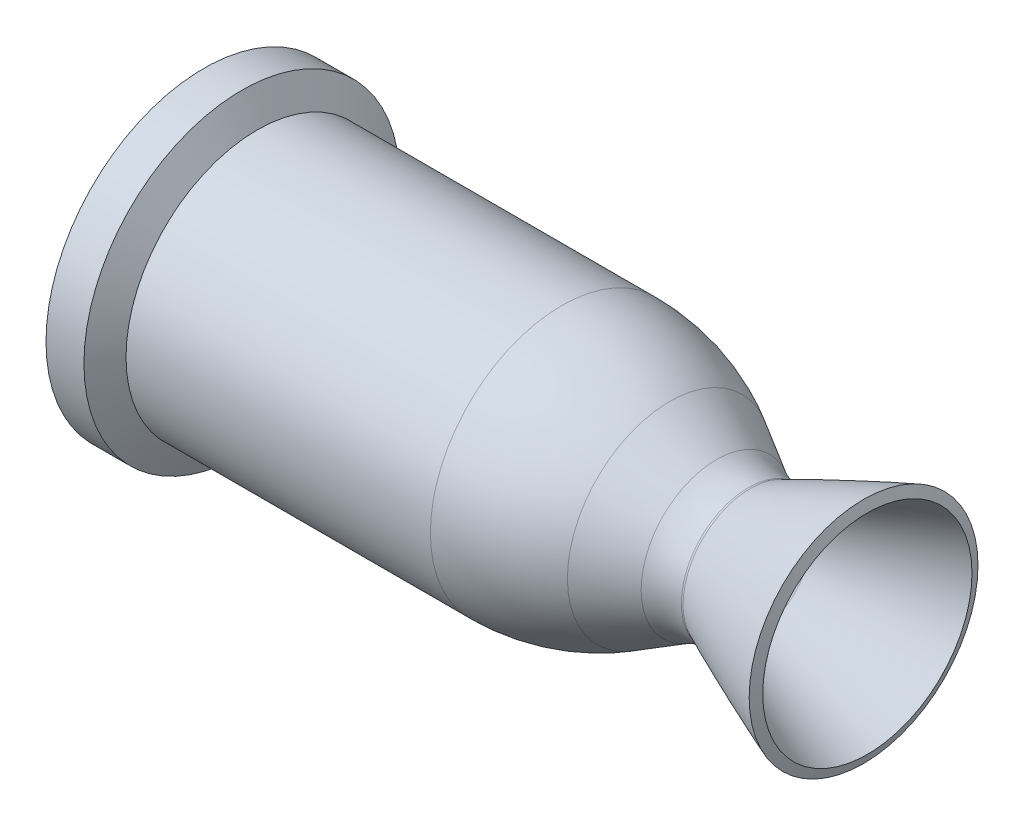
SolidWorks part; units mm, degrees
ref_plane "Front Plane" through (0, 0, 0) normal (0, 0, 1) x (1, 0, 0)
ref_plane "Top Plane" through (0, 0, 0) normal (0, 1, 0) x (1, 0, 0)
ref_plane "Right Plane" through (0, 0, 0) normal (1, 0, 0) x (0, 0, -1)
sketch "Sketch2" plane through (0, 0, 0) normal (0, 0, 1) x (1, 0, 0)
  line L0 (0, 55.5012) -> (144.9347, 55.5012)
  line L1 (192.877, 42.655) -> (215.1271, 29.8089)
  line L2 (0, 0) -> (370.4363, 0) construction
  line L3 (0, 0) -> (0, 55.5012) construction
  line L4 (0, 0) -> (290.4856, 0) construction
  line L5 (290.4856, 0) -> (290.4856, 47.6713) construction
  arc A0 (192.877, 42.655) -> (144.9347, 55.5012) centre (144.9346, -40.3836) ccw
  arc A1 (215.1271, 29.8089) -> (233.7428, 24.8208) centre (233.7428, 62.0521) ccw
  arc A2 (233.7428, 24.8208) -> (237.5976, 25.6398) centre (233.7428, 34.3024) ccw
  spline S0 degree 2 poles (237.5976, 25.6398) (305.7949, 55.9872) (370.4363, 74.9571) knots 0 0 0 1 1 1
  dimension "D4" = 95.8847
  dimension "D5" = 37.2313
  dimension "D6" = 9.4816
  dimension "D1" = 111.0023
  dimension "D2" = 49.6417
  dimension "D3" = 149.9142
  dimension "D7" = 144.9347
  dimension "D8" = 233.7428
  dimension "D9" = 370.4363
  dimension "D10" = 192.877
  dimension "D11" = 215.1271
  dimension "D12" = 237.5976
  dimension "D13" = 30
  dimension "D14" = 290.4856
sketch "Sketch3" plane through (0, 0, 0) normal (0, 0, 1) x (1, 0, 0)
  line L3 (0, 62.5012) -> (144.9347, 62.5012)
  line L4 (196.377, 48.7172) -> (218.6271, 35.871)
  line L5 (193.877, 44.3871) -> (216.1272, 31.5409)
  line L6 (0, 57.5012) -> (144.9347, 57.5012)
  line L7 (193.877, 44.3871) -> (216.1272, 31.5409)
  line L8 (0, 57.5012) -> (144.9347, 57.5012)
  line L9 (0, 57.5012) -> (0, 62.5012)
  line L11 (290.4856, 49.816) -> (288.682, 54.4794)
  arc A3 (196.377, 48.7172) -> (144.9347, 62.5012) centre (144.9346, -40.3836) ccw
  arc A4 (218.6271, 35.871) -> (233.7428, 31.8208) centre (233.7428, 62.0521) ccw
  arc A5 (233.7428, 31.8208) -> (234.7517, 32.0352) centre (233.7428, 34.3024) ccw
  arc A6 (233.7428, 26.8208) -> (236.7845, 27.467) centre (233.7428, 34.3024) ccw
  arc A7 (216.1272, 31.5409) -> (233.7428, 26.8208) centre (233.7428, 62.0521) ccw
  arc A8 (193.877, 44.3871) -> (144.9347, 57.5012) centre (144.9346, -40.3836) ccw
  arc A9 (233.7428, 26.8208) -> (236.7845, 27.467) centre (233.7428, 34.3024) ccw
  arc A10 (216.1272, 31.5409) -> (233.7428, 26.8208) centre (233.7428, 62.0521) ccw
  arc A11 (193.877, 44.3871) -> (144.9347, 57.5012) centre (144.9346, -40.3836) ccw
  spline S0 degree 3 poles (-1790.66, -2153.2376) (311.3728, 932.0911) (1413.5943, 873.7916) (1556.1742, -2407.1411) knots -11.442491 -11.442491 -11.442491 -11.442491 17.487929 17.487929 17.487929 17.487929 only from (236.7845, 27.467) to (369.8731, 76.8762)
  spline S1 degree 3 poles (236.7845, 27.467) (254.8702, 35.5151) (272.7706, 42.9648) (290.4856, 49.816) knots 0 0 0 0 0.397158 0.397158 0.397158 0.397158
  spline S2 degree 1 poles (234.7517, 32.0352) (288.682, 54.4794) knots 0 0 1 1 construction
  spline S3 degree 3 poles (234.7517, 32.0352) (237.0156, 33.0426) (241.558, 35.0478) (250.5989, 38.9738) (261.8653, 43.7444) (273.0698, 48.3257) (282.0056, 51.8808) (286.452, 53.6169) (288.682, 54.4794) knots 0 0 0 0 0.049645 0.09929 0.198579 0.297869 0.347514 0.397158 0.397158 0.397158 0.397158
  dimension "D3" = 288.682
  dimension "D1" = 2
  dimension "D2" = 5
revolve "Revolve1" add sketch "Sketch3" angle 360 about L2
sketch "Sketch4" plane through (0, 0, 0) normal (0, 0, 1) x (1, 0, 0)
  line L0 (144.9347, 62.5012) -> (0, 62.5012) construction
  line L1 (144.9347, 62.5012) -> (0, 62.5012) construction
  line L5 (-25.4, 57.5012) -> (-25.4, 75.2012)
  line L6 (0, 62.5012) -> (-7.3323, 75.2012)
  line L7 (-25.4, 75.2012) -> (-7.3323, 75.2012)
  line L11 (0, 62.5012) -> (0, 57.5012)
  line L12 (0, 57.5012) -> (-25.4, 57.5012)
  point P9 (0, 0)
  point P11 (0, 0)
  point P12 (0, 0)
  point P13 (0, 0)
  dimension "D1" = 25.4
  dimension "D2" = 12.7
  dimension "D3" = 120
  dimension "D4" = 5
revolve "Revolve5" add sketch "Sketch4" angle 360 about L2
